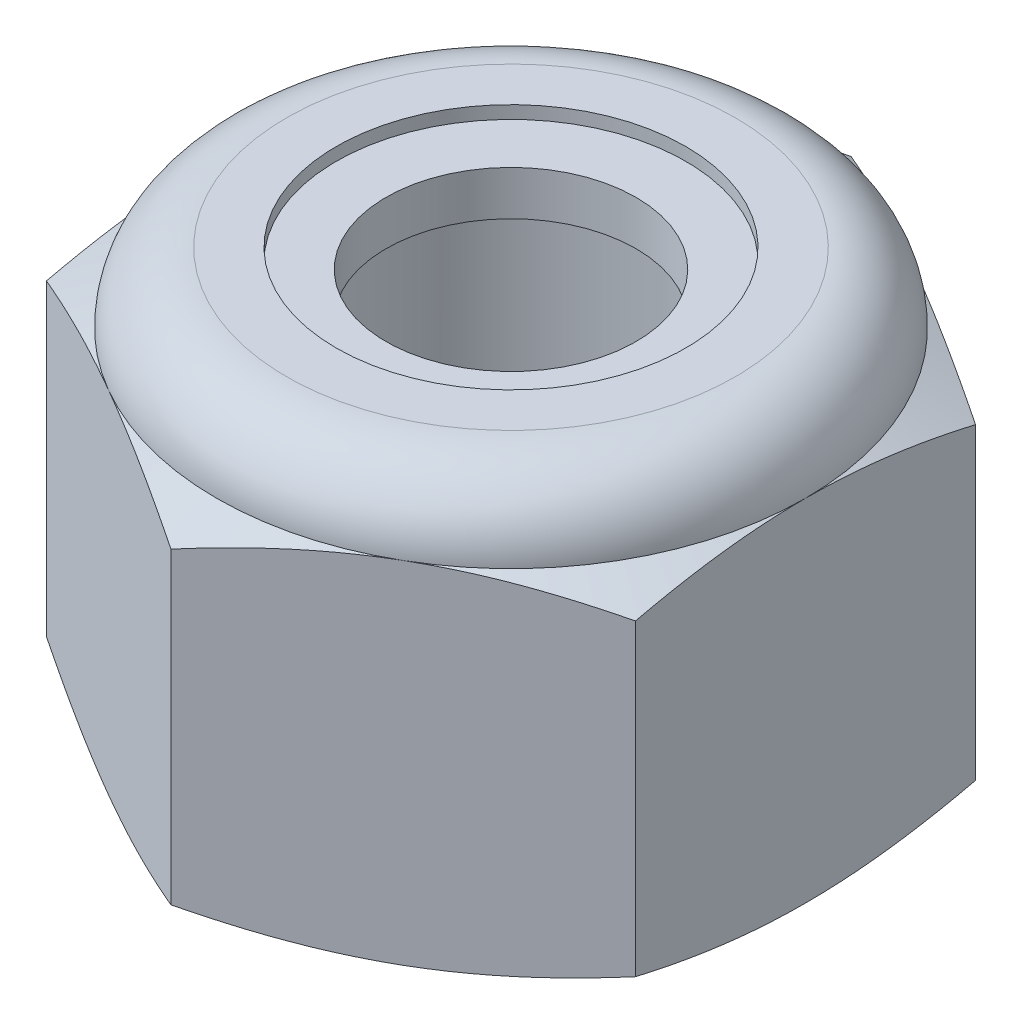
SolidWorks part; units mm, degrees
ref_plane "Front" through (0, 0, 0) normal (0, 0, 1) x (1, 0, 0)
ref_plane "Top" through (0, 0, 0) normal (0, 1, 0) x (1, 0, 0)
ref_plane "Right" through (0, 0, 0) normal (1, 0, 0) x (0, 0, -1)
sketch "Sketch1" plane through (0, 0, 0) normal (0, 1, 0) x (1, 0, 0)
  line L0 (0, 0) -> (1.4142, -1.4142) construction
  line L1 (0, 4.0415) -> (-3.5, 2.0207)
  line L2 (-3.5, 2.0207) -> (-3.5, -2.0207)
  line L3 (-3.5, -2.0207) -> (0, -4.0415)
  line L4 (0, -4.0415) -> (3.5, -2.0207)
  line L5 (3.5, -2.0207) -> (3.5, 2.0207)
  line L6 (3.5, 2.0207) -> (0, 4.0415)
  circle A0 centre (0, 0) radius 3.5 construction
  circle A1 centre (0, 0) radius 2
  point P12 (1.4142, -1.4142)
  dimension "Thread Dia" = 4
  dimension "Hex Flats" = 7
  dimension "D1" = 45
extrude "Extrude1" add sketch "Sketch1" along normal blind 5
chamfer "Chamfer1" distance 0.2 angle 45 1 edges at (0, 0, 2)
sketch "Sketch5" plane through (0, 0, 0) normal (1, 0, 0) x (0, 0, -1)
  line L0 (0, 0) -> (3.5, 0)
  line L1 (3.5, 0) -> (4.0415, 0.2525)
  line L2 (4.0415, 0.2525) -> (4.0415, 3.9142)
  line L3 (4.0415, 3.9142) -> (3.5, 4.1667)
  line L4 (2.6667, 5) -> (2.6667, 6.27)
  line L5 (2.6667, 6.27) -> (5.3115, 6.27)
  line L6 (5.3115, 6.27) -> (5.3115, -1.27)
  line L7 (5.3115, -1.27) -> (0, -1.27)
  line L8 (0, -1.27) -> (0, 0)
  line L9 (3.5, 4.1667) -> (3.5, 0) construction
  line L10 (2.0207, 5) -> (4.0415, 5) construction
  line L13 (4.0415, 2.0833) -> (5.3115, 2.0833) construction
  line L14 (4.0415, 5) -> (4.0415, 0) construction
  line L15 (0, 0) -> (0, 6.27) construction
  line L20 (0, 6.27) -> (2.6667, 6.27) construction
  arc A0 (3.5, 4.1667) -> (2.6667, 5) centre (2.6667, 4.1667) ccw
  dimension "D1" = 25
  dimension "D2" = 1.27
  dimension "D3" = 5
  dimension "D4" = 0.8333
revolve "Cut-Revolve3" cut sketch "Sketch5" angle 360 about L15
sketch "Sketch6" plane through (0, 0, 0) normal (1, 0, 0) x (0, 0, -1)
  line L0 (0, 4.1667) -> (3.3476, 4.1667)
  line L1 (2.6667, 4.8476) -> (2.0762, 4.8476)
  line L2 (0, 6.27) -> (0, 4.1667)
  line L3 (2.0762, 6.27) -> (0, 6.27)
  line L4 (0, 6.27) -> (2.6667, 6.27) construction
  line L5 (0, 0) -> (0, 6.27) construction
  line L6 (0, 6.27) -> (0, 0) construction
  line L7 (2.0762, 4.8476) -> (2.0762, 6.27)
  line L8 (2.6667, 5) -> (2.6667, 4.8476) construction
  line L9 (2.0762, 4.8476) -> (1.9238, 4.8476) construction
  line L21 (2, 4.8476) -> (2, 5) construction
  arc A0 (3.3476, 4.1667) -> (2.6667, 4.8476) centre (2.6667, 4.1667) ccw
  arc A1 (3.5, 4.1667) -> (2.6667, 5) centre (2.6667, 4.1667) ccw construction
  dimension "D1" = 0.1524
revolve "Cut-Revolve4" cut sketch "Sketch6" angle 360 about L6
sketch "Sketch7" plane through (0, 0, 0) normal (1, 0, 0) x (0, 0, -1)
  line L0 (1.4857, 4.2429) -> (3.2666, 4.2429)
  line L1 (2.6667, 4.7714) -> (1.4857, 4.7714)
  line L2 (1.4857, 4.7714) -> (1.4857, 4.2429)
  line L3 (1.4857, 4.2429) -> (0, 4.2429) construction
  line L4 (0, 4.2429) -> (0, 4.7714) construction
  line L5 (0, 4.7714) -> (1.4857, 4.7714) construction
  line L6 (1.4857, 4.2429) -> (1.4857, 4.1667) construction
  line L7 (0, 4.1667) -> (3.3476, 4.1667) construction
  line L8 (2.6667, 4.7714) -> (2.6667, 4.8476) construction
  line L10 (1.4857, 4.8476) -> (2.0762, 4.8476) construction
  line L11 (2.6667, 4.8476) -> (2.0762, 4.8476) construction
  arc A0 (3.2666, 4.2429) -> (2.6667, 4.7714) centre (2.6667, 4.1667) ccw
  arc A2 (3.3476, 4.1667) -> (2.6667, 4.8476) centre (2.6667, 4.1667) ccw construction
  dimension "D1" = 0.0762
revolve "Revolve2" add sketch "Sketch7" angle 360 about L4
ref_axis "Center Axis 1" through (0, 4.1667, 0) along (0, -1, 0)
equation "\"D4@Sketch5\"=\"Height@Extrude1\"/6"
equation "\"D1@Chamfer1\"=.05*\"Thread Dia@Sketch1\""
